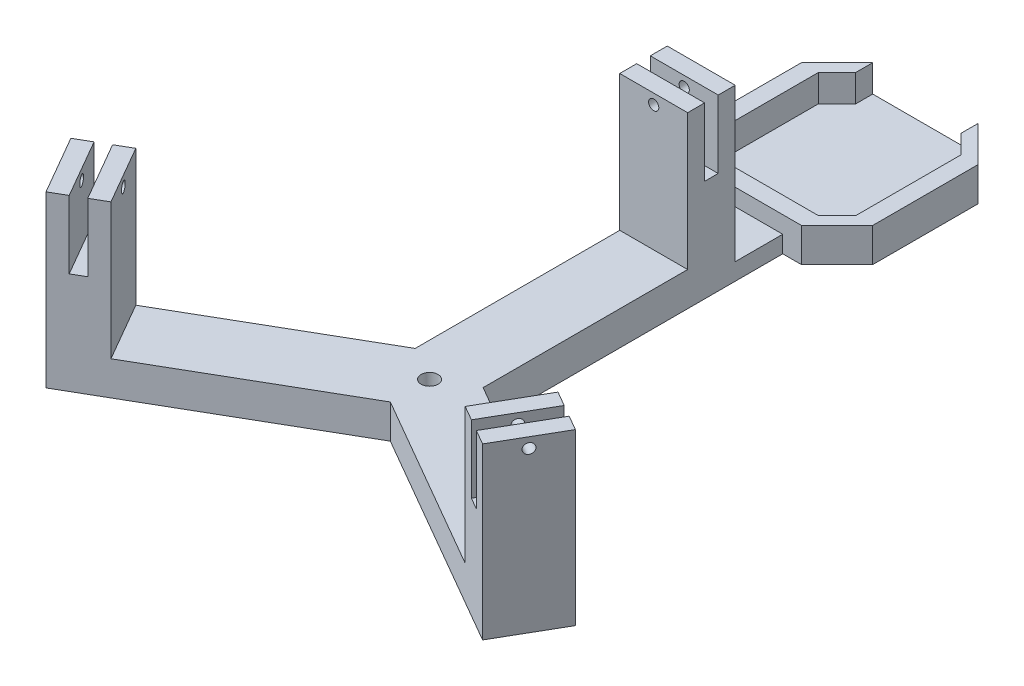
SolidWorks part; units mm, degrees
ref_plane "Front Plane" through (0, 0, 0) normal (0, 0, 1) x (1, 0, 0)
ref_plane "Top Plane" through (0, 0, 0) normal (0, 1, 0) x (1, 0, 0)
ref_plane "Right Plane" through (0, 0, 0) normal (1, 0, 0) x (0, 0, -1)
sketch "Sketch1" plane through (0, 0, 0) normal (0, 1, 0) x (1, 0, 0)
  line L0 (0, 0) -> (-10, 5.7735)
  line L1 (-10, 5.7735) -> (-10, 80)
  line L2 (-10, 80) -> (10, 80)
  line L3 (10, 80) -> (10, 5.7735)
  line L4 (10, 5.7735) -> (0, 0)
  dimension "D1" = 120
  dimension "D2" = 20
  dimension "D3" = 80
extrude "Boss-Extrude1" add sketch "Sketch1" along normal blind 10
sketch "Sketch2" plane through (0, 10, 0) normal (0, 1, 0) x (1, 0, 0)
  line L0 (10, 5.7735) -> (10, 80) construction
  line L1 (-10, 80) -> (10, 80)
  line L2 (-10, 80) -> (-10, 66)
  line L3 (-10, 66) -> (10, 66)
  line L4 (10, 80) -> (10, 66)
  dimension "D1" = 14
extrude "Boss-Extrude2" add sketch "Sketch2" along normal blind 20
sketch "Sketch3" plane through (0, 30, 0) normal (0, 1, 0) x (1, 0, 0)
  line L0 (10, 66) -> (10, 80) construction
  line L1 (-10, 80) -> (10, 80)
  line L2 (-10, 80) -> (-10, 75)
  line L3 (-10, 75) -> (10, 75)
  line L4 (10, 80) -> (10, 75)
  line L6 (-10, 66) -> (10, 66)
  line L7 (-10, 66) -> (-10, 71)
  line L8 (-10, 71) -> (10, 71)
  line L9 (10, 66) -> (10, 71)
  dimension "D1" = 5
  dimension "D2" = 5
extrude "Boss-Extrude3" add sketch "Sketch3" along normal blind 20
sketch "Sketch4" plane through (0, 0, -66) normal (0, 0, 1) x (1, 0, 0)
  line L0 (-10, 50) -> (-10, 10) construction
  line L1 (-10, 50) -> (10, 50) construction
  circle A0 centre (0, 47) radius 1.5
  dimension "D3" = 3
  dimension "D1" = 10
  dimension "D2" = 3
extrude "Cut-Extrude1" cut sketch "Sketch4" against normal through all both and the other way through all
pattern_circular "CirPattern1" count 3 over 360 about axis through (0, 10, 0) along (0, -1, 0) of "Boss-Extrude2", "Cut-Extrude1", "Boss-Extrude1", "Boss-Extrude3"
sketch "Sketch5" plane through (0, 10, 0) normal (0, 1, 0) x (1, 0, 0)
  circle A0 centre (0, 0) radius 2.5
  dimension "D1" = 5
extrude "Cut-Extrude2" cut sketch "Sketch5" against normal through all
sketch "Sketch6" plane through (0, 0, 0) normal (0, -1, 0) x (1, 0, 0)
  circle A0 centre (0, 0) radius 2.5 construction
  dimension "D1" = 5
sketch "Sketch8" plane through (0, 0, 0) normal (0, 1, 0) x (1, 0, 0)
  line L10 (-10, 80) -> (10, 80)
  line L11 (-10, 80) -> (-10, 94)
  line L12 (-10, 94) -> (10, 94)
  line L13 (10, 80) -> (10, 94)
  dimension "D2" = 14
  dimension "D13" = 20
sketch "Sketch11" plane through (0, 0, 0) normal (0, 1, 0) x (1, 0, 0)
  line L9 (-15.5, 94) -> (15.5, 94)
  line L14 (15.5, 94) -> (26, 104.5)
  line L15 (26, 104.5) -> (26, 135.5)
  line L16 (26, 135.5) -> (15.5, 146)
  line L17 (15.5, 146) -> (-15.5, 146)
  line L18 (-15.5, 146) -> (-26, 135.5)
  line L19 (-26, 135.5) -> (-26, 104.5)
  line L20 (-26, 104.5) -> (-15.5, 94)
  dimension "D2" = 31
  dimension "D3" = 52
  dimension "D4" = 52
  dimension "D5" = 31
  dimension "D6" = 10.5
  dimension "D7" = 10.5
  dimension "D8" = 94
  dimension "D11" = 26
extrude "Boss-Extrude7" add sketch "Sketch8" along normal blind 5
extrude "Boss-Extrude8" add sketch "Sketch11" along normal blind 10
sketch "Sketch12" plane through (0, 10, 0) normal (0, 1, 0) x (1, 0, 0)
  line L0 (-21, 104.5) -> (-21, 135.5)
  line L2 (-15.5, 141) -> (15.5, 141) construction
  line L3 (15.5, 141) -> (21, 135.5)
  line L4 (21, 135.5) -> (21, 104.5)
  line L5 (21, 104.5) -> (15.5, 99)
  line L6 (15.5, 99) -> (-15.5, 99)
  line L7 (-15.5, 99) -> (-21, 104.5)
  line L8 (-21, 135.5) -> (-15.5, 141)
  line L9 (-15.5, 141) -> (-15.5, 146)
  line L10 (15.5, 146) -> (-15.5, 146) construction
  line L11 (15.5, 141) -> (15.5, 146)
  line L12 (-15.5, 146) -> (15.5, 146)
  point P2 (0, 0)
  point P13 (0, 0)
  point P14 (0, 0)
  point P18 (0, 0)
  point P19 (0, 0)
  point P20 (0, 0)
  dimension "D1" = 42
  dimension "D2" = 42
  dimension "D3" = 135
extrude "Cut-Extrude3" cut sketch "Sketch12" against normal blind 8
